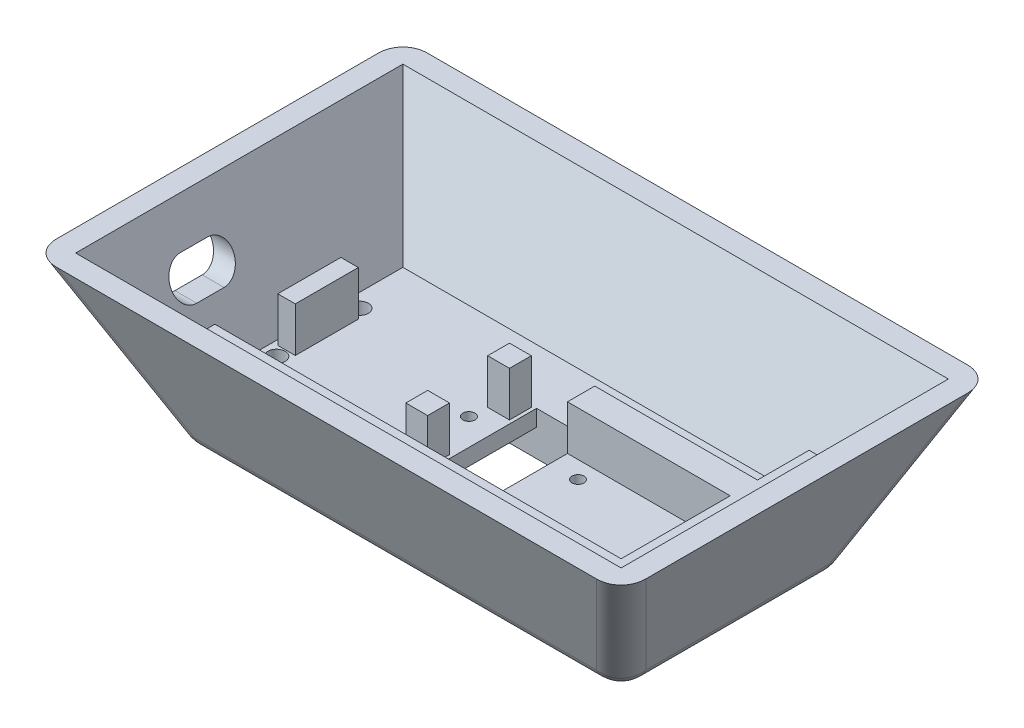
SolidWorks part; units mm, degrees
ref_plane "Front Plane" through (0, 0, 0) normal (0, 0, 1) x (1, 0, 0)
ref_plane "Top Plane" through (0, 0, 0) normal (0, 1, 0) x (1, 0, 0)
ref_plane "Right Plane" through (0, 0, 0) normal (1, 0, 0) x (0, 0, -1)
sketch "Sketch1" plane through (0, 0, 0) normal (0, 1, 0) x (1, 0, 0)
  line L1 (-40, 20) -> (40, 20)
  line L2 (-40, 20) -> (-40, -20)
  line L3 (-40, -20) -> (40, -20)
  line L4 (40, 20) -> (40, -20)
  line L5 (-40, 20) -> (40, -20) construction
  line L6 (-40, -20) -> (40, 20) construction
  point P0 (0, 0)
  dimension "D1" = 40
  dimension "D2" = 80
extrude "Boss-Extrude1" add sketch "Sketch1" along normal blind 30 draft 25 draft outward yes
sketch "Sketch2" plane through (0, 0, 0) normal (0, -1, 0) x (1, 0, 0)
  line L0 (0, 9.6) -> (0, 20) construction
  line L1 (-15.1, 9.6) -> (15.1, 9.6)
  line L2 (-15.1, 9.6) -> (-15.1, -9.6)
  line L3 (-15.1, -9.6) -> (15.1, -9.6)
  line L4 (15.1, 9.6) -> (15.1, -9.6)
  line L5 (-15.1, 9.6) -> (15.1, -9.6) construction
  line L6 (-15.1, -9.6) -> (15.1, 9.6) construction
  line L7 (-40, 20) -> (40, 20) construction
  point P0 (0, 0)
  dimension "D1" = 19.2
  dimension "D2" = 30.2
  dimension "D3" = 10.4
extrude "Cut-Extrude1" cut sketch "Sketch2" against normal blind 5
sketch "Sketch3" plane through (0, 30, 0) normal (0, 1, 0) x (1, 0, 0)
  line L17 (-49.9892, 29.9892) -> (-49.9892, -29.9892)
  line L18 (-49.9892, -29.9892) -> (49.9892, -29.9892)
  line L19 (49.9892, -29.9892) -> (49.9892, 29.9892)
  line L20 (49.9892, 29.9892) -> (-49.9892, 29.9892)
  line L21 (-49.9892, 29.9892) -> (-49.9892, -29.9892)
  line L22 (-49.9892, -29.9892) -> (49.9892, -29.9892)
  line L23 (49.9892, -29.9892) -> (49.9892, 29.9892)
  line L24 (49.9892, 29.9892) -> (-49.9892, 29.9892)
  dimension "D2" = 4
extrude "Cut-Extrude3" cut sketch "Sketch3" against normal blind 22 draft 25
sketch "Sketch5" plane through (0, 5, 0) normal (0, -1, 0) x (1, 0, 0)
  line L0 (0, -2.1) -> (-10, -2.1) construction
  line L1 (0, -2.1) -> (10, -2.1) construction
  line L2 (-5.1, 5.6) -> (-5.1, 9.6) construction
  line L3 (15.1, 9.6) -> (-15.1, 9.6) construction
  line L4 (-5.1, 9.6) -> (4.9, 9.6) construction
  line L5 (-15.1, 9.6) -> (-15.1, -9.6) construction
  line L6 (4.9, 9.6) -> (-5.1, 9.6)
  line L7 (4.9, 9.6) -> (4.9, -9.6)
  line L8 (4.9, -9.6) -> (-5.1, -9.6)
  line L9 (-5.1, 9.6) -> (-5.1, -9.6)
  line L11 (-15.1, -9.6) -> (15.1, -9.6) construction
  circle A0 centre (-10, -2.1) radius 1.1
  circle A1 centre (10, -2.1) radius 1.1
  dimension "D3" = 2.2
  dimension "D4" = 2.2
  dimension "D1" = 10
  dimension "D2" = 10
  dimension "D5" = 4
  dimension "D6" = 10
  dimension "D7" = 7.5
  dimension "D9" = 10
extrude "Cut-Extrude4" cut sketch "Sketch5" against normal up to next
sketch "Sketch6" plane through (0, 8, 0) normal (0, 1, 0) x (1, 0, 0)
  line L0 (-5.1, 0) -> (-39.7305, 0) construction
  line L1 (-5.1, -9.6) -> (-5.1, 9.6) construction
  line L2 (-39.7305, 19.7305) -> (-39.7305, -19.7305) construction
  line L3 (-39.7305, 0) -> (-39.7305, -8.7) construction
  line L4 (-39.7305, -8.7) -> (-1.7305, -8.7) construction
  line L5 (-39.7305, 0) -> (-39.7305, 12.3) construction
  line L6 (-39.7305, -8.7) -> (-39.7305, -5.98) construction
  line L7 (-39.7305, 12.3) -> (-1.7305, 12.3)
  line L8 (-39.7305, 12.3) -> (-39.7305, -8.7)
  line L9 (-39.7305, -8.7) -> (-1.7305, -8.7)
  line L10 (-1.7305, 12.3) -> (-1.7305, -8.7)
  line L11 (-39.7305, -5.98) -> (-37.1905, -5.98) construction
  line L12 (-39.7305, -8.7) -> (-39.7305, 9.27) construction
  line L13 (-39.7305, 9.27) -> (-37.1905, 9.27) construction
  line L14 (-39.7305, -5.98) -> (-3.7305, -5.98) construction
  circle A0 centre (-37.1905, -5.98) radius 1.6
  circle A1 centre (-37.1905, 9.27) radius 1.6
  dimension "D2" = 3.2
extrude "PCB_HeatSetInserts" cut sketch "Sketch6" against normal blind 4.75 contours A1 | A0
sketch "Sketch7" plane through (0, 8, 0) normal (0, 1, 0) x (1, 0, 0)
  line L0 (-9.7305, -5.7305) -> (-5.7305, -5.7305)
  line L1 (-38.7905, 9.27) -> (-38.7905, -5.98) construction
  line L2 (-35.5905, 9.27) -> (-35.5905, -5.98) construction
  line L3 (-37.1905, 7.67) -> (-37.1905, 6.92) construction
  line L4 (-37.1905, -4.38) -> (-37.1905, -4.13) construction
  line L5 (-9.7305, -5.7305) -> (-9.7305, -9.7305)
  line L6 (-38.7905, 7.42) -> (-35.5905, 7.42)
  line L7 (-38.7905, 7.42) -> (-38.7905, -4.13)
  line L8 (-38.7905, -4.13) -> (-35.5905, -4.13)
  line L9 (-35.5905, 7.42) -> (-35.5905, -4.13)
  line L10 (-9.7305, 9.2695) -> (-5.7305, 9.2695)
  line L11 (-9.7305, 9.2695) -> (-9.7305, 5.2695)
  line L12 (-9.7305, 5.2695) -> (-5.7305, 5.2695)
  line L13 (-5.7305, 9.2695) -> (-5.7305, 5.2695)
  line L14 (-9.7305, -9.7305) -> (-5.7305, -9.7305)
  line L15 (-5.7305, -5.7305) -> (-5.7305, -9.7305)
  line L16 (-37.1905, -5.98) -> (-39.7305, -5.98) construction
  line L17 (-37.1905, -5.98) -> (-37.1905, -8.7) construction
  line L18 (-39.7305, 19.7305) -> (-39.7305, -19.7305) construction
  line L19 (-39.7305, -8.7) -> (-9.7305, -8.7) construction
  line L20 (-9.7305, -8.7) -> (-9.7305, -7.7) construction
  line L21 (-9.7305, -5.7305) -> (-9.7305, 5.2695) construction
  line L22 (-39.7305, -19.7305) -> (-39.7305, -14.7305)
  line L23 (-39.7305, -14.7305) -> (34.7305, -14.7305)
  line L24 (34.7305, -14.7305) -> (34.7305, 5.2695)
  line L25 (34.7305, 5.2695) -> (4.9, 5.2695)
  line L26 (4.9, 9.6) -> (4.9, -9.6) construction
  line L27 (4.9, 5.2695) -> (4.9, 10.2695)
  line L28 (4.9, 10.2695) -> (34.7305, 10.2695)
  line L29 (34.7305, 10.2695) -> (34.7305, 19.7305)
  line L30 (39.7305, 19.7305) -> (-39.7305, 19.7305) construction
  line L31 (34.7305, 19.7305) -> (39.7305, 19.7305)
  line L32 (39.7305, 19.7305) -> (39.7305, -19.7305)
  line L33 (39.7305, -19.7305) -> (-39.7305, -19.7305)
  circle A0 centre (-37.1905, 9.27) radius 1.6 construction
  circle A1 centre (-37.1905, 9.27) radius 1.6 construction
  circle A2 centre (-37.1905, -5.98) radius 1.6 construction
  circle A3 centre (-37.1905, -5.98) radius 1.6 construction
  point P31 (-39.7305, -8.7)
  dimension "D1" = 0.75
  dimension "D2" = 2.54
  dimension "D3" = 2.72
  dimension "D4" = 30
  dimension "D5" = 4
  dimension "D6" = 4
  dimension "D7" = 4
  dimension "D8" = 4
  dimension "D9" = 11
  dimension "D10" = 1
  dimension "D11" = 5
  dimension "D12" = 5
  dimension "D13" = 20
  dimension "D14" = 5
extrude "Boss-Extrude3" add sketch "Sketch7" along normal blind 8.2
sketch "Sketch10" plane through (-35.5905, 0, 0) normal (1, 0, 0) x (0, 0, -1)
  line L0 (1.645, 8) -> (1.645, 20.25) construction
  line L1 (1.645, 20.25) -> (-17.105, 20.25) construction
  line L2 (-13.855, 20.25) -> (-8.855, 20.25) construction
  line L3 (-13.855, 23.5) -> (-8.855, 23.5)
  line L4 (-13.855, 17) -> (-8.855, 17)
  line L5 (1.645, 20.25) -> (-11.355, 20.25) construction
  line L6 (-4.13, 8) -> (7.42, 8) construction
  arc A0 (-13.855, 23.5) -> (-13.855, 17) centre (-13.855, 20.25) ccw
  arc A1 (-8.855, 17) -> (-8.855, 23.5) centre (-8.855, 20.25) ccw
  point P6 (-11.355, 20.25)
  point P13 (0, 0)
  point P14 (0, 0)
  dimension "D1" = 12.25
  dimension "D3" = 5
  dimension "D2" = 18.75
  dimension "D4" = 6.5
extrude "USB-C Cutout" cut sketch "Sketch10" against normal up to next contours L4 A1 L3 A0
fillet "Fillet1" radius 5 8 edges at (-40, 0, 0) (0, 0, 20) (40, 0, 0) (0, 0, -20) (-46.9946, 15, 26.9946) (46.9946, 15, 26.9946) (46.9946, 15, -26.9946) (-46.9946, 15, -26.9946)
